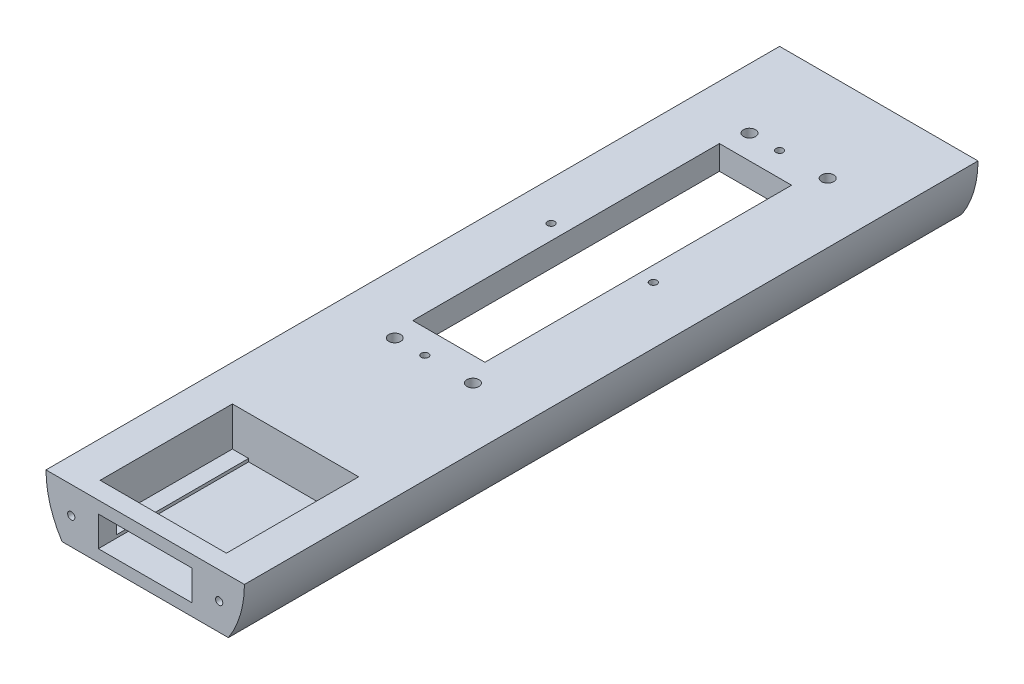
SolidWorks part; units mm, degrees
ref_plane "前视基准面" through (0, 0, 0) normal (0, 0, 1) x (1, 0, 0)
ref_plane "上视基准面" through (0, 0, 0) normal (0, 1, 0) x (1, 0, 0)
ref_plane "右视基准面" through (0, 0, 0) normal (1, 0, 0) x (0, 0, -1)
other "Configuration Table"
sketch "草图1" plane through (0, 0, 0) normal (0, 1, 0) x (1, 0, 0)
  line L1 (0, 0) -> (33, 0)
  line L2 (0, 0) -> (0, -122)
  line L3 (0, -122) -> (33, -122)
  line L4 (33, 0) -> (33, -122)
  dimension "D1" = 33
  dimension "D2" = 122
extrude "凸台-拉伸1" add sketch "草图1" along normal blind 9
sketch "草图2" plane through (0, 0, 0) normal (0, -1, 0) x (1, 0, 0)
  line L0 (0, 0) -> (0, 122) construction
  line L1 (9, 70) -> (21, 70)
  line L2 (9, 70) -> (9, 19)
  line L3 (9, 19) -> (21, 19)
  line L4 (21, 70) -> (21, 19)
  line L5 (33, 122) -> (33, 0) construction
  line L6 (33, 0) -> (0, 0) construction
  line L7 (0, 122) -> (33, 122) construction
  line L8 (6, 119) -> (27, 119)
  line L9 (6, 119) -> (6, 97)
  line L10 (6, 97) -> (27, 97)
  line L11 (27, 119) -> (27, 97)
  dimension "D1" = 51
  dimension "D2" = 9
  dimension "D3" = 12
  dimension "D4" = 19
  dimension "D5" = 6
  dimension "D6" = 6
  dimension "D7" = 3
  dimension "D8" = 22
extrude "切除-拉伸1" cut sketch "草图2" against normal through all
extrude "凸台-拉伸2" add sketch "草图2<2>" against normal blind 2.5 contours L10 L11 L8 L9
sketch "草图2<2>" plane through (0, 0, 0) normal (0, -1, 0) x (1, 0, 0) same geometry as "草图2"
sketch "草图3" plane through (0, 0, 0) normal (0, -1, 0) x (1, 0, 0)
  line L0 (9, 70) -> (9, 19) construction
  line L1 (4, 78) -> (26, 78)
  line L2 (4, 78) -> (4, 11)
  line L3 (4, 11) -> (26, 11)
  line L4 (26, 78) -> (26, 11)
  line L5 (21, 19) -> (21, 70) construction
  line L6 (9, 19) -> (21, 19) construction
  line L7 (21, 70) -> (9, 70) construction
  dimension "D1" = 5
  dimension "D2" = 5
  dimension "D3" = 8
  dimension "D4" = 8
extrude "切除-拉伸2" cut sketch "草图3" against normal blind 5
sketch "草图4" plane through (0, 5, 0) normal (0, -1, 0) x (1, 0, 0)
  circle A0 centre (23, 74) radius 1
  circle A1 centre (10, 74) radius 1
  circle A2 centre (10, 74) radius 2
  circle A3 centre (23, 74) radius 2
  circle A4 centre (23, 15) radius 2
  circle A5 centre (23, 15) radius 1
  circle A6 centre (10, 15) radius 2
  circle A7 centre (10, 15) radius 1
  dimension "D1" = 4
  dimension "D2" = 2
extrude "切除-拉伸3" cut sketch "草图4" against normal through all contours A1 | A0 | A5 | A7
extrude "切除-拉伸4" cut sketch "草图4<3>" against normal blind 2 contours A2 | A3 | A4 | A6
sketch "草图4<3>" plane through (0, 5, 0) normal (0, -1, 0) x (1, 0, 0) same geometry as "草图4"
sketch "草图5" plane through (0, 5, 0) normal (0, -1, 0) x (1, 0, 0)
  line L0 (15, 78) -> (15, 70) construction
  line L1 (26, 78) -> (4, 78) construction
  line L2 (9, 70) -> (21, 70) construction
  line L3 (15, 11) -> (15, 19) construction
  line L4 (4, 11) -> (26, 11) construction
  line L5 (21, 19) -> (9, 19) construction
  line L6 (4, 44.5) -> (9, 44.5) construction
  line L7 (4, 78) -> (4, 11) construction
  line L8 (9, 19) -> (9, 70) construction
  line L9 (26, 44.5) -> (21, 44.5) construction
  line L10 (26, 11) -> (26, 78) construction
  line L11 (21, 70) -> (21, 19) construction
  circle A0 centre (15, 74) radius 0.6
  circle A1 centre (6.5, 44.5) radius 0.6
  circle A2 centre (23.5, 44.5) radius 0.6
  circle A3 centre (15, 15) radius 0.6
  dimension "D1" = 1.2
extrude "切除-拉伸5" cut sketch "草图5" against normal through all
sketch "草图6" plane through (0, 0, 122) normal (0, 0, 1) x (1, 0, 0)
  line L0 (0, 9) -> (33, 9) construction
  circle A0 centre (16.5, 9) radius 16.5
  dimension "D1" = 33
extrude "切除-拉伸6" cut sketch "草图6" against normal through all flip side to cut
sketch "草图7" plane through (0, 0, 122) normal (0, 0, 1) x (1, 0, 0)
  line L0 (8.7, 7) -> (0, 9) construction
  line L1 (8.7, 7) -> (24.3, 7)
  line L2 (8.7, 7) -> (8.7, 2)
  line L3 (8.7, 2) -> (24.3, 2)
  line L4 (24.3, 7) -> (24.3, 2)
  line L5 (0, 9) -> (33, 9) construction
  line L6 (24.3, 7) -> (33, 9) construction
  line L8 (4.2, 4.5) -> (8.7, 4.5) construction
  line L9 (24.3, 4.5) -> (28.8, 4.5) construction
  arc A0 (30.3293, 0) -> (33, 9) centre (16.5, 9) ccw construction
  circle A1 centre (4.2, 4.5) radius 0.6
  circle A2 centre (28.8, 4.5) radius 0.6
  dimension "D4" = 1.2
  dimension "D1" = 8.7
  dimension "D2" = 7
  dimension "D3" = 2
  dimension "D5" = 4.5
extrude "切除-拉伸7" cut sketch "草图7" against normal up to surface (25 mm away) contours L1 L4 L3 L2 up to face at (16.5, 5.75, 97)
extrude "切除-拉伸8" cut sketch "草图7<3>" against normal blind 3 contours A1 | A2
sketch "草图7<3>" plane through (0, 0, 122) normal (0, 0, 1) x (1, 0, 0) same geometry as "草图7"
